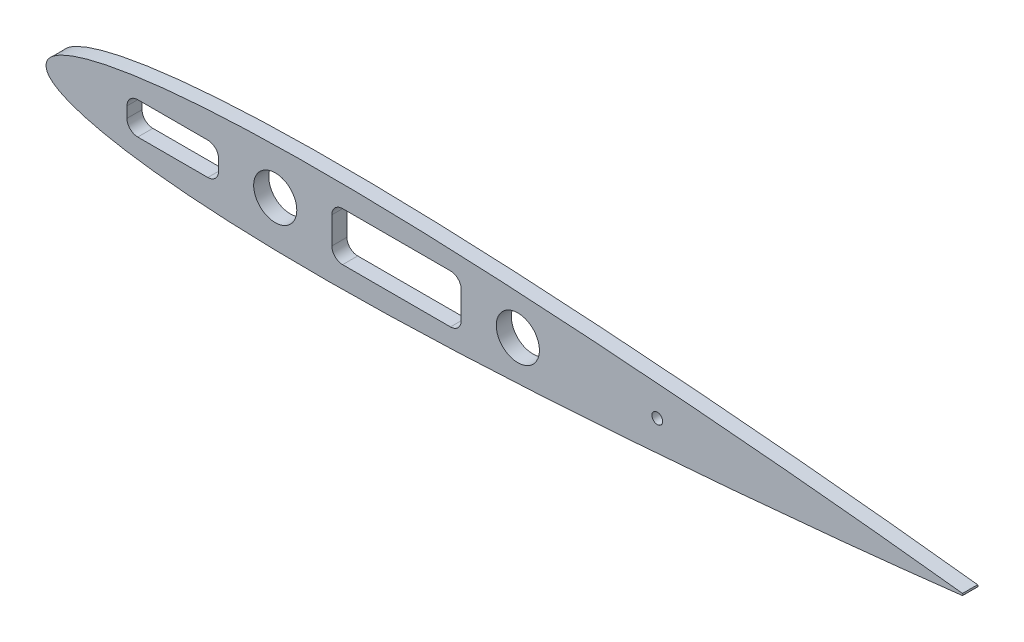
SolidWorks part; units mm, degrees
material "Фанера"
ref_plane "Front Plane" through (0, 0, 0) normal (0, 0, 1) x (1, 0, 0)
ref_plane "Top Plane" through (0, 0, 0) normal (0, 1, 0) x (1, 0, 0)
ref_plane "Right Plane" through (0, 0, 0) normal (1, 0, 0) x (0, 0, -1)
curve "Кривая1"
  spline degree 3 poles (110, 0, 0) (110.0276, -0.2367, 0) (110.0855, -0.7342, 0) (110.5302, -1.4271, 0) (111.1963, -2.0786, 0) (112.1098, -2.7013, 0) (113.2568, -3.2993, 0) (114.6379, -3.8731, 0) (116.2477, -4.4214, 0) (118.0813, -4.9426, 0) (120.1331, -5.4348, 0) (122.3972, -5.8961, 0) (124.8672, -6.3247, 0) (127.537, -6.7187, 0) (130.3997, -7.0764, 0) (133.4488, -7.3965, 0) (136.6771, -7.6776, 0) (140.0777, -7.9187, 0) (143.6433, -8.119, 0) (147.3662, -8.278, 0) (151.2389, -8.3955, 0) (155.2534, -8.4715, 0) (159.4016, -8.5065, 0) (163.6751, -8.501, 0) (168.0653, -8.456, 0) (172.5632, -8.3725, 0) (177.1595, -8.252, 0) (181.8446, -8.096, 0) (186.6087, -7.9062, 0) (191.4413, -7.6846, 0) (196.3316, -7.4331, 0) (201.2684, -7.1538, 0) (206.2396, -6.8489, 0) (211.233, -6.5205, 0) (216.2352, -6.1709, 0) (221.2323, -5.8022, 0) (226.2093, -5.417, 0) (231.1504, -5.0174, 0) (236.0382, -4.6058, 0) (240.8542, -4.1849, 0) (245.5777, -3.7574, 0) (250.1862, -3.3262, 0) (254.6542, -2.8948, 0) (258.9526, -2.4672, 0) (263.0477, -2.0479, 0) (266.899, -1.6426, 0) (270.4558, -1.2586, 0) (273.6512, -0.9053, 0) (276.3854, -0.5964, 0) (278.4526, -0.359, 0) (279.592, -0.2261, 0) (280, -0.1785, 0) knots 0 0 0 0 0.004099 0.008615 0.013935 0.020278 0.027753 0.03641 0.046266 0.05732 0.069559 0.082963 0.097507 0.113164 0.129903 0.14769 0.166492 0.186272 0.206992 0.228612 0.251092 0.274389 0.298458 0.323254 0.348728 0.37483 0.401509 0.42871 0.456376 0.484448 0.512864 0.541558 0.570462 0.599504 0.628607 0.65769 0.686667 0.715445 0.743924 0.771995 0.79954 0.826428 0.852512 0.877624 0.901571 0.924121 0.944989 0.963804 0.980044 0.992855 1 1 1 1
curve "Кривая2"
  spline degree 3 poles (280, 0.1785, 0) (279.592, 0.2261, 0) (278.4526, 0.359, 0) (276.3854, 0.5964, 0) (273.6512, 0.9053, 0) (270.4558, 1.2586, 0) (266.899, 1.6426, 0) (263.0477, 2.0479, 0) (258.9526, 2.4672, 0) (254.6542, 2.8948, 0) (250.1862, 3.3262, 0) (245.5777, 3.7574, 0) (240.8542, 4.1849, 0) (236.0382, 4.6058, 0) (231.1504, 5.0174, 0) (226.2093, 5.417, 0) (221.2323, 5.8022, 0) (216.2352, 6.1709, 0) (211.233, 6.5205, 0) (206.2396, 6.8489, 0) (201.2684, 7.1538, 0) (196.3316, 7.4331, 0) (191.4413, 7.6846, 0) (186.6087, 7.9062, 0) (181.8446, 8.096, 0) (177.1595, 8.252, 0) (172.5632, 8.3725, 0) (168.0653, 8.456, 0) (163.6751, 8.501, 0) (159.4016, 8.5065, 0) (155.2534, 8.4715, 0) (151.2389, 8.3955, 0) (147.3662, 8.278, 0) (143.6433, 8.119, 0) (140.0777, 7.9187, 0) (136.6771, 7.6776, 0) (133.4488, 7.3965, 0) (130.3997, 7.0764, 0) (127.537, 6.7187, 0) (124.8672, 6.3247, 0) (122.3972, 5.8961, 0) (120.1331, 5.4348, 0) (118.0813, 4.9426, 0) (116.2477, 4.4214, 0) (114.6379, 3.8731, 0) (113.2568, 3.2993, 0) (112.1098, 2.7013, 0) (111.1963, 2.0786, 0) (110.5302, 1.4271, 0) (110.0855, 0.7342, 0) (110.0276, 0.2367, 0) (110, 0, 0) knots 0 0 0 0 0.007145 0.019956 0.036196 0.055011 0.075879 0.098429 0.122376 0.147488 0.173572 0.20046 0.228005 0.256076 0.284555 0.313333 0.34231 0.371393 0.400496 0.429538 0.458442 0.487136 0.515552 0.543624 0.57129 0.598491 0.62517 0.651272 0.676746 0.701542 0.725611 0.748908 0.771388 0.793008 0.813728 0.833508 0.85231 0.870097 0.886836 0.902493 0.917037 0.930441 0.94268 0.953734 0.96359 0.972247 0.979722 0.986065 0.991385 0.995901 1 1 1 1
sketch "Эскиз1" plane through (0, 0, 0) normal (0, 0, 1) x (1, 0, 0)
  line L0 (105.1708, 0) -> (280.7263, 0) construction
  line L1 (280.0739, 0) -> (280.0739, 24.3846) construction
  line L2 (110, -5.3315) -> (110, 17.5304) construction
  line L3 (152.5185, 18.8331) -> (152.5185, -21.3473) construction
  line L4 (223.3826, 13.2402) -> (223.3826, -18.4275) construction
  line L5 (217.7476, 6.0581) -> (217.7476, -6.0581)
  line L6 (127.0185, -3) -> (140.0185, -3)
  line L7 (125.0185, -1) -> (125.0185, 1)
  line L8 (127.0185, 3) -> (140.0185, 3)
  line L9 (142.0185, -1) -> (142.0185, 1)
  line L10 (125.0185, -3) -> (142.0185, 3) construction
  line L11 (125.0185, 3) -> (142.0185, -3) construction
  line L12 (165.0185, -4.5) -> (185.0185, -4.5)
  line L13 (163.0185, -2.5) -> (163.0185, 2.5)
  line L14 (165.0185, 4.5) -> (185.0185, 4.5)
  line L15 (187.0185, -2.5) -> (187.0185, 2.5)
  line L16 (163.0185, -4.5) -> (187.0185, 4.5) construction
  line L17 (163.0185, 4.5) -> (187.0185, -4.5) construction
  arc A0 (280, 0.1785) -> (280, -0.1785) centre (279.8215, 0) cw
  circle A1 centre (152.5185, 0) radius 4
  circle A2 centre (197.5185, 0) radius 4
  arc A3 (185.0185, 4.5) -> (187.0185, 2.5) centre (185.0185, 2.5) cw
  arc A4 (185.0185, -4.5) -> (187.0185, -2.5) centre (185.0185, -2.5) ccw
  arc A5 (165.0185, -4.5) -> (163.0185, -2.5) centre (165.0185, -2.5) cw
  arc A6 (163.0185, 2.5) -> (165.0185, 4.5) centre (165.0185, 2.5) cw
  arc A7 (125.0185, 1) -> (127.0185, 3) centre (127.0185, 1) cw
  arc A8 (127.0185, -3) -> (125.0185, -1) centre (127.0185, -1) cw
  arc A9 (140.0185, -3) -> (142.0185, -1) centre (140.0185, -1) ccw
  arc A10 (140.0185, 3) -> (142.0185, 1) centre (140.0185, 1) cw
  arc A11 (223.3826, 5.635) -> (223.3826, -5.635) centre (223.3826, 0) ccw
  circle A12 centre (223.3826, 0) radius 1
  spline S0 degree 3 poles (-2755.954, -885.3814) (181.7249, 41.6654) (105.0139, 7.1675) (110.5302, -1.4271) (111.1963, -2.0786) (112.1098, -2.7013) (113.2568, -3.2993) (114.6379, -3.8731) (116.2477, -4.4214) (118.0813, -4.9426) (120.1331, -5.4348) (122.3972, -5.8961) (124.8672, -6.3247) (127.537, -6.7187) (130.3997, -7.0764) (133.4488, -7.3965) (136.6771, -7.6776) (140.0777, -7.9187) (143.6433, -8.119) (147.3662, -8.278) (151.2389, -8.3955) (155.2534, -8.4715) (159.4016, -8.5065) (163.6751, -8.501) (168.0653, -8.456) (172.5632, -8.3725) (177.1595, -8.252) (181.8446, -8.096) (186.6087, -7.9062) (191.4413, -7.6846) (196.3316, -7.4331) (201.2684, -7.1538) (206.2396, -6.8489) (211.233, -6.5205) (216.2352, -6.1709) (221.2323, -5.8022) (226.2093, -5.417) (231.1504, -5.0174) (236.0382, -4.6058) (240.8542, -4.1849) (247.0711, -3.6222) (253.1161, -3.0479) (258.9526, -2.4672) (263.0477, -2.0479) (266.899, -1.6426) (270.4558, -1.2586) (273.6512, -0.9053) (276.3854, -0.5964) (371.3591, 10.3142) (463.8587, 34.4359) (902.2965, -2926.9188) knots -0.158926 -0.158926 -0.158926 -0.158926 0.004099 0.008615 0.013935 0.020278 0.027753 0.03641 0.046266 0.05732 0.069559 0.082963 0.097507 0.113164 0.129903 0.14769 0.166492 0.186272 0.206992 0.228612 0.251092 0.274389 0.298458 0.323254 0.348728 0.37483 0.401509 0.42871 0.456376 0.484448 0.512864 0.541558 0.570462 0.599504 0.628607 0.65769 0.686667 0.715445 0.743924 0.771995 0.79954 0.852512 0.877624 0.901571 0.924121 0.944989 0.963804 0.980044 0.992855 2.626789 2.626789 2.626789 2.626789 only from (110, 0) to (280, -0.1785) construction
  spline S1 degree 3 poles (902.2917, 2926.8865) (463.8581, -34.4357) (371.3587, -10.3142) (276.3854, 0.5964) (273.6512, 0.9053) (270.4558, 1.2586) (266.899, 1.6426) (263.0477, 2.0479) (258.9526, 2.4672) (253.1161, 3.0479) (247.0711, 3.6222) (240.8542, 4.1849) (236.0382, 4.6058) (231.1504, 5.0174) (226.2093, 5.417) (221.2323, 5.8022) (216.2352, 6.1709) (211.233, 6.5205) (206.2396, 6.8489) (201.2684, 7.1538) (196.3316, 7.4331) (191.4413, 7.6846) (186.6087, 7.9062) (181.8446, 8.096) (177.1595, 8.252) (172.5632, 8.3725) (168.0653, 8.456) (163.6751, 8.501) (159.4016, 8.5065) (155.2534, 8.4715) (151.2389, 8.3955) (147.3662, 8.278) (143.6433, 8.119) (140.0777, 7.9187) (136.6771, 7.6776) (133.4488, 7.3965) (130.3997, 7.0764) (127.537, 6.7187) (124.8672, 6.3247) (122.3972, 5.8961) (120.1331, 5.4348) (118.0813, 4.9426) (116.2477, 4.4214) (114.6379, 3.8731) (113.2568, 3.2993) (112.1098, 2.7013) (111.1963, 2.0786) (110.5302, 1.4271) (105.0141, -7.1673) (181.7207, -41.6635) (-2755.7067, 885.3033) knots -1.626783 -1.626783 -1.626783 -1.626783 0.007145 0.019956 0.036196 0.055011 0.075879 0.098429 0.122376 0.147488 0.20046 0.228005 0.256076 0.284555 0.313333 0.34231 0.371393 0.400496 0.429538 0.458442 0.487136 0.515552 0.543624 0.57129 0.598491 0.62517 0.651272 0.676746 0.701542 0.725611 0.748908 0.771388 0.793008 0.813728 0.833508 0.85231 0.870097 0.886836 0.902493 0.917037 0.930441 0.94268 0.953734 0.96359 0.972247 0.979722 0.986065 0.991385 0.995901 1.158921 1.158921 1.158921 1.158921 only from (280, 0.1785) to (110, 0) construction
  spline S2 degree 3 poles (110, 0) (110.0276, -0.2367) (110.0855, -0.7342) (110.5302, -1.4271) (111.1963, -2.0786) (112.1098, -2.7013) (113.2568, -3.2993) (114.6379, -3.8731) (116.2477, -4.4214) (118.0813, -4.9426) (120.1331, -5.4348) (122.3972, -5.8961) (124.8672, -6.3247) (127.537, -6.7187) (130.3997, -7.0764) (133.4488, -7.3965) (136.6771, -7.6776) (140.0777, -7.9187) (143.6433, -8.119) (147.3662, -8.278) (151.2389, -8.3955) (155.2534, -8.4715) (159.4016, -8.5065) (163.6751, -8.501) (168.0653, -8.456) (172.5632, -8.3725) (177.1595, -8.252) (181.8446, -8.096) (186.6087, -7.9062) (191.4413, -7.6846) (196.3316, -7.4331) (201.2684, -7.1538) (206.2396, -6.8489) (211.233, -6.5205) (216.2352, -6.1709) (221.2323, -5.8022) (226.2093, -5.417) (231.1504, -5.0174) (236.0382, -4.6058) (240.8542, -4.1849) (247.0711, -3.6222) (253.1161, -3.0479) (258.9526, -2.4672) (263.0477, -2.0479) (266.899, -1.6426) (270.4558, -1.2586) (273.6512, -0.9053) (276.3854, -0.5964) (278.4526, -0.359) (279.592, -0.2261) (280, -0.1785) knots 0 0 0 0 0.004099 0.008615 0.013935 0.020278 0.027753 0.03641 0.046266 0.05732 0.069559 0.082963 0.097507 0.113164 0.129903 0.14769 0.166492 0.186272 0.206992 0.228612 0.251092 0.274389 0.298458 0.323254 0.348728 0.37483 0.401509 0.42871 0.456376 0.484448 0.512864 0.541558 0.570462 0.599504 0.628607 0.65769 0.686667 0.715445 0.743924 0.771995 0.79954 0.852512 0.877624 0.901571 0.924121 0.944989 0.963804 0.980044 0.992855 1 1 1 1
  spline S3 degree 3 poles (280, 0.1785) (279.592, 0.2261) (278.4526, 0.359) (276.3854, 0.5964) (273.6512, 0.9053) (270.4558, 1.2586) (266.899, 1.6426) (263.0477, 2.0479) (258.9526, 2.4672) (253.1161, 3.0479) (247.0711, 3.6222) (240.8542, 4.1849) (236.0382, 4.6058) (231.1504, 5.0174) (226.2093, 5.417) (221.2323, 5.8022) (216.2352, 6.1709) (211.233, 6.5205) (206.2396, 6.8489) (201.2684, 7.1538) (196.3316, 7.4331) (191.4413, 7.6846) (186.6087, 7.9062) (181.8446, 8.096) (177.1595, 8.252) (172.5632, 8.3725) (168.0653, 8.456) (163.6751, 8.501) (159.4016, 8.5065) (155.2534, 8.4715) (151.2389, 8.3955) (147.3662, 8.278) (143.6433, 8.119) (140.0777, 7.9187) (136.6771, 7.6776) (133.4488, 7.3965) (130.3997, 7.0764) (127.537, 6.7187) (124.8672, 6.3247) (122.3972, 5.8961) (120.1331, 5.4348) (118.0813, 4.9426) (116.2477, 4.4214) (114.6379, 3.8731) (113.2568, 3.2993) (112.1098, 2.7013) (111.1963, 2.0786) (110.5302, 1.4271) (110.0855, 0.7342) (110.0276, 0.2367) (110, 0) knots 0 0 0 0 0.007145 0.019956 0.036196 0.055011 0.075879 0.098429 0.122376 0.147488 0.20046 0.228005 0.256076 0.284555 0.313333 0.34231 0.371393 0.400496 0.429538 0.458442 0.487136 0.515552 0.543624 0.57129 0.598491 0.62517 0.651272 0.676746 0.701542 0.725611 0.748908 0.771388 0.793008 0.813728 0.833508 0.85231 0.870097 0.886836 0.902493 0.917037 0.930441 0.94268 0.953734 0.96359 0.972247 0.979722 0.986065 0.991385 0.995901 1 1 1 1
  point P19 (175.0185, 0)
  point P22 (133.5185, 0)
  point P31 (223.3826, -5.635)
  point P54 (223.3826, 5.635)
  point P55 (223.3826, -5.635)
  point P56 (223.3826, 5.635)
  point P63 (217.7476, 6.0581)
  point P64 (217.7476, -6.0581)
  dimension "D1" = 0.2524
  dimension "D3" = 8
  dimension "D13" = 2
  dimension "D14" = 5.635
  dimension "D15" = 2
  dimension "D2" = 170.0739
  dimension "D4" = 42.5185
  dimension "D5" = 56.6913
  dimension "D6" = 45
  dimension "D7" = 6
  dimension "D8" = 17
  dimension "D9" = 19
  dimension "D10" = 22.5
  dimension "D11" = 9
  dimension "D12" = 24
extrude "Бобышка-Вытянуть1" add sketch "Эскиз1" along normal mid plane 2.8 contours A11 S3 S2 L8 A10 L9 A9 L6 A8 L7 A7 L13 A6 L14 A3 L15 A4 L12 A5 A1 A2 | A0 S3 A11 S2 A12 | L5 S2 A11 | A11 S3 L5 region at (219.1006, 4.5865, 0) region at (216.6568, 3.0291, 0) region at (219.1006, -4.5865, 0) region at (240.7174, 0, 0)
equation "\"D4@Эскиз1\"=\"D2@Эскиз1\"/4"
equation "\"D5@Эскиз1\"=\"D2@Эскиз1\"/3"
equation "\"D10@Эскиз1\"=\"D6@Эскиз1\"/2"
